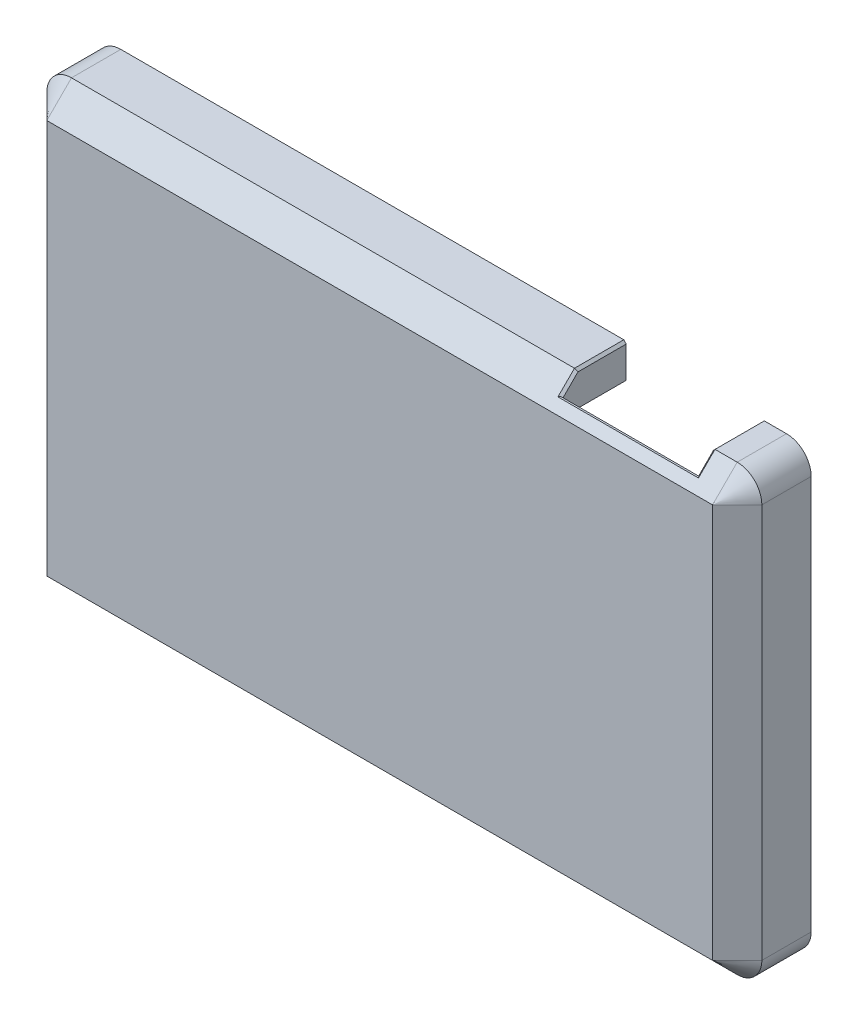
SolidWorks part; units mm, degrees
material "1060 合金"
ref_plane "前视基准面" through (0, 0, 0) normal (0, 0, 1) x (1, 0, 0)
ref_plane "上视基准面" through (0, 0, 0) normal (0, 1, 0) x (1, 0, 0)
ref_plane "右视基准面" through (0, 0, 0) normal (1, 0, 0) x (0, 0, -1)
sketch "草图1" plane through (0, 0, 0) normal (0, 0, 1) x (1, 0, 0)
  line L1 (-29, -18) -> (29, -18)
  line L2 (-29, -18) -> (-29, 18)
  line L3 (-29, 18) -> (29, 18)
  line L4 (29, -18) -> (29, 18)
  line L5 (-29, -18) -> (29, 18) construction
  line L6 (-29, 18) -> (29, -18) construction
  point P0 (0, 0)
  dimension "D1" = 58
  dimension "D2" = 36
extrude "凸台-拉伸1" add sketch "草图1" along normal blind 6
sketch "草图2" plane through (0, 0, 0) normal (0, 0, -1) x (-1, 0, 0)
  line L1 (-26.25, -15.25) -> (26.25, -15.25)
  line L2 (-26.25, -15.25) -> (-26.25, 15.25)
  line L3 (-26.25, 15.25) -> (26.25, 15.25)
  line L4 (26.25, -15.25) -> (26.25, 15.25)
  line L5 (-26.25, -15.25) -> (26.25, 15.25) construction
  line L6 (-26.25, 15.25) -> (26.25, -15.25) construction
  point P0 (0, 0)
  dimension "D1" = 52.5
  dimension "D2" = 30.5
extrude "切除-拉伸1" cut sketch "草图2" against normal blind 5.2
fillet "圆角1" radius 2 4 edges at (-29, 18, 3) (-29, -18, 3) (29, 18, 3) (29, -18, 3)
sketch "草图3" plane through (0, 0, 5.2) normal (0, 0, -1) x (-1, 0, 0)
  line L0 (26.25, 15.25) -> (-26.25, 15.25) construction
  line L1 (15.25, 15.25) -> (11.25, 15.25)
  line L2 (15.25, 15.25) -> (15.25, -15.25)
  line L3 (15.25, -15.25) -> (11.25, -15.25)
  line L4 (11.25, 15.25) -> (11.25, -15.25)
  line L5 (-26.25, -15.25) -> (26.25, -15.25) construction
  line L7 (26.25, -15.25) -> (26.25, 15.25) construction
  dimension "D1" = 4
  dimension "D2" = 11
extrude "凸台-拉伸2" add sketch "草图3" along normal blind 3.7
fillet "圆角2" radius 4 4 edges at (-15.25, -15.25, 3.35) (-11.25, -15.25, 3.35) (-15.25, 15.25, 3.35) (-11.25, 15.25, 3.35)
chamfer "倒角1" distance 2 angle 45 8 edges at (0, -18, 6) (28.4142, -17.4142, 6) (-28.4142, -17.4142, 6) (29, 0, 6) (-29, 0, 6) (28.4142, 17.4142, 6) (-28.4142, 17.4142, 6) (0, 18, 6)
sketch "草图4" plane through (0, 18, 0) normal (0, 1, 0) x (1, 0, 0)
  line L0 (29, 0) -> (29, -4) construction
  line L1 (14, 0) -> (25, 0)
  line L2 (14, 0) -> (14, -5.2)
  line L3 (14, -5.2) -> (25, -5.2)
  line L4 (25, 0) -> (25, -5.2)
  line L5 (14, 0) -> (25, -5.2) construction
  line L6 (14, -5.2) -> (25, 0) construction
  line L7 (27, 0) -> (-27, 0) construction
  point P0 (19.5, -2.6)
  dimension "D1" = 11
  dimension "D2" = 4
  dimension "D3" = 5.2
extrude "切除-拉伸2" cut sketch "草图4" against normal blind 10
fillet "圆角3" radius 0.2 4 edges at (26.25, -15.25, 2.6) (26.25, 15.25, 2.6) (-26.25, -15.25, 2.6) (-26.25, 15.25, 2.6)
chamfer "倒角2" distance 0.2 angle 45 5 edges at (25, 18, 2) (25, 17.4, 4.6) (19.5, 16.8, 5.2) (14, 17.4, 4.6) (14, 18, 2) first distance on face at (26, 18, 2) first distance on face at (9.75, 17.2, 4.8) first distance on face at (-6.5, 18, 2)
sketch "草图5" plane through (0, 0, 0) normal (0, 0, -1) x (-1, 0, 0)
  line L1 (-27.5, -16.5) -> (27.5, -16.5) construction
  line L2 (-27.5, -16.5) -> (-27.5, 16.5) construction
  line L3 (-27.5, 16.5) -> (27.5, 16.5) construction
  line L4 (27.5, -16.5) -> (27.5, 16.5) construction
  line L5 (-27.5, -16.5) -> (27.5, 16.5) construction
  line L6 (-27.5, 16.5) -> (27.5, -16.5) construction
  point P0 (0, 0)
  dimension "D1" = 55
  dimension "D2" = 33
hole_wizard "M1.2x0.25 螺纹孔1" positions "3D草图1" profile "草图6" tap size "M1.2x0.25" standard "GB"
sketch3d "3D草图1"
  point P0 (27.5, 16.5, 0)
  point P3 (27.5, -16.5, 0)
  point P6 (-27.5, -16.5, 0)
  point P12 (-27.5, 16.5, 0)
sketch "草图6" plane through (27.5, 16.5, 0) normal (1, 0, 0) x (0, 1, 0)
  line L0 (0, 0) -> (0, 3.2854)
  line L1 (0, 3.2854) -> (0.475, 3)
  line L2 (0.475, 3) -> (0.475, 0)
  line L5 (0.475, 0) -> (0, 0)
  line L10 (0, 3.2854) -> (-0.475, 3) construction
  line L11 (0, -6.35) -> (0, 107.95) construction
  dimension "螺纹孔钻头直径" = 0.95
  dimension "螺纹孔钻头深度" = 3
  dimension "导头角度" = 118
cosmetic thread "孔螺蚊线5" parameters "D1"=2.4, "D2"=1.2
cosmetic thread "孔螺蚊线6" parameters "D1"=2.4, "D2"=1.2
cosmetic thread "孔螺蚊线7" parameters "D1"=2.4, "D2"=1.2
cosmetic thread "孔螺蚊线8" parameters "D1"=2.4, "D2"=1.2
